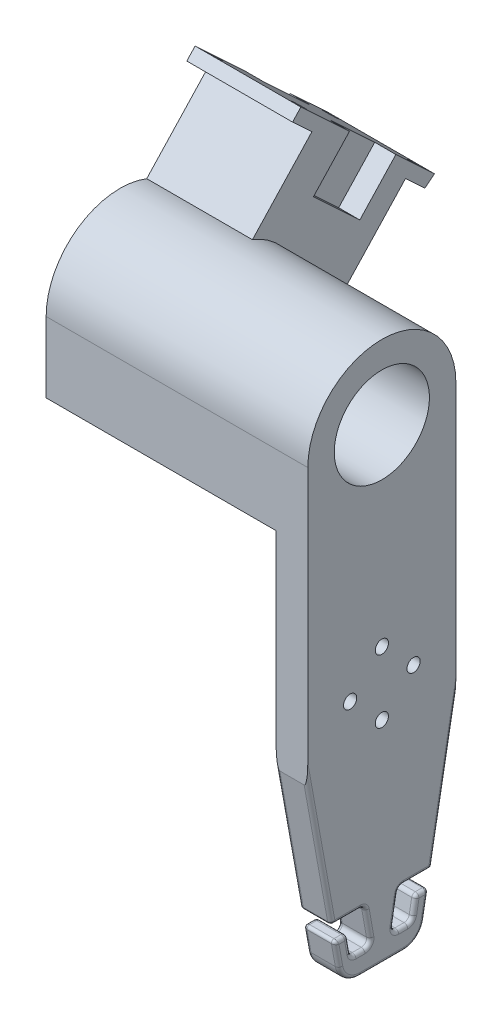
SolidWorks part; units mm, degrees
ref_plane "前视基准面" through (0, 0, 0) normal (0, 0, 1) x (1, 0, 0)
ref_plane "上视基准面" through (0, 0, 0) normal (0, 1, 0) x (1, 0, 0)
ref_plane "右视基准面" through (0, 0, 0) normal (1, 0, 0) x (0, 0, -1)
other "Configuration Table"
sketch "草图1" plane through (0, 0, 0) normal (0, 1, 0) x (1, 0, 0)
  line L1 (-15, 14) -> (15, 14)
  line L2 (-15, 14) -> (-15, -14)
  line L3 (-15, -14) -> (15, -14)
  line L4 (15, 14) -> (15, -14)
  line L5 (-15, 14) -> (15, -14) construction
  line L6 (-15, -14) -> (15, 14) construction
  point P0 (0, 0)
  dimension "D1" = 30
  dimension "D2" = 28
extrude "凸台-拉伸1" add sketch "草图1" along normal blind 67
sketch "草图2" plane through (-15, 0, 0) normal (-1, 0, 0) x (0, 0, 1)
  line L0 (-14, 0) -> (14, 0) construction
  line L1 (-14, 33.5) -> (14, 33.5) construction
  line L2 (-14, 67) -> (-14, 0) construction
  line L3 (14, 67) -> (14, 0) construction
  circle A0 centre (0, 10) radius 8.25
  circle A1 centre (0, 57) radius 8.25
  dimension "D2" = 16.5
  dimension "D1" = 10
extrude "切除-拉伸1" cut sketch "草图2" against normal blind 2.5
sketch "草图3" plane through (-15, 0, 0) normal (-1, 0, 0) x (0, 0, 1)
  point P0 (0, 57)
  point P1 (0, 10)
sketch "草图4" plane through (-12.5, 0, 0) normal (-1, 0, 0) x (0, 0, 1)
  circle A1 centre (0, 57) radius 8.25
  circle A2 centre (0, 57) radius 8.25
  dimension "D1" = 0
extrude "凸台-拉伸2" add sketch "草图4" along normal blind 4
sketch "草图5" plane through (-15, 0, 0) normal (-1, 0, 0) x (0, 0, 1)
  line L0 (14, 67) -> (14, 0) construction
  line L1 (-14, 67) -> (14, 67)
  line L2 (-14, 67) -> (-14, 39)
  line L3 (-14, 39) -> (14, 39)
  line L4 (14, 67) -> (14, 39)
  dimension "D1" = 28
extrude "凸台-拉伸3" add sketch "草图5" along normal blind 33.5
ref_plane "基准面1" through (0, 24.1802, 25.9301) normal (0, 0.682, 0.7314) x (-1, 0, 0)
ref_plane "基准面2" through (0, 42.8198, -39.9301) normal (0, 0.7314, -0.682) x (-1, 0, 0)
ref_plane "基准面3" through (0, 68.0515, -63.459) normal (0, 0.7314, -0.682) x (-1, 0, 0)
sketch "草图6" plane through (0, 68.0515, -63.459) normal (0, 0.7314, -0.682) x (-1, 0, 0)
  line L0 (48.5, 55.9328) -> (-15, 55.9328) construction
  line L10 (34.5, 55.9328) -> (62.5, 55.9328)
  line L11 (34.5, 55.9328) -> (34.5, 16.359)
  line L14 (34.5, 16.359) -> (62.5, 16.359)
  line L15 (62.5, 55.9328) -> (62.5, 16.359)
  line L16 (48.5, 16.359) -> (15, 16.359) construction
  line L17 (62.5, 55.9328) -> (34.5, 16.359) construction
  line L18 (34.5, 55.9328) -> (62.5, 16.359) construction
  line L20 (48.5, 55.9328) -> (48.5, 35.4549) construction
  point P10 (48.5, 36.1459)
  dimension "D1" = 28
extrude "凸台-拉伸4" add sketch "草图6" against normal up to vertex (74.0739 mm away) up to point (-48.5, 39, 14)
sketch "草图10" plane through (-34.5, 0, 0) normal (1, 0, 0) x (0, 0, -1)
  line L3 (14, 39) -> (-14, 39)
  line L4 (-14, 39) -> (0.9766, 25.0341)
  line L5 (0.9766, 25.0341) -> (14, 39)
  line L6 (14, 39) -> (-14, 39)
  line L7 (-14, 39) -> (0.9766, 25.0341)
  line L8 (0.9766, 25.0341) -> (14, 39)
  dimension "D1" = 0
extrude "切除-拉伸4" cut sketch "草图10" against normal through all
sketch "草图11" plane through (-34.5, 0, 0) normal (1, 0, 0) x (0, 0, -1)
  line L3 (-14, 39) -> (-14, 67)
  line L4 (-14, 67) -> (-27.9659, 52.0234)
  line L5 (-27.9659, 52.0234) -> (-14, 39)
  line L6 (-14, 39) -> (-14, 67)
  line L7 (-14, 67) -> (-27.9659, 52.0234)
  line L8 (-27.9659, 52.0234) -> (-14, 39)
  dimension "D1" = 0
extrude "切除-拉伸5" cut sketch "草图11" against normal through all
sketch "草图12" plane through (0, 0, -14) normal (0, 0, -1) x (-1, 0, 0)
  line L0 (15, 39) -> (15, 0) construction
  line L1 (-15, 0) -> (9, 0)
  line L2 (-15, 0) -> (-15, 73.4763)
  line L3 (-15, 73.4763) -> (9, 73.4763)
  line L4 (9, 0) -> (9, 73.4763)
  dimension "D1" = 6
extrude "切除-拉伸6" cut sketch "草图12" against normal through all
sketch "草图13" plane through (-12.5, 0, 0) normal (-1, 0, 0) x (0, 0, 1)
  line L0 (0, 18.25) -> (0, 1.75) construction
  line L1 (-8.25, 10) -> (8.25, 10) construction
  circle A0 centre (0, 10) radius 8.25 construction
  circle A1 centre (0, 10) radius 8.25 construction
  circle A2 centre (0, 16) radius 1.25
  circle A3 centre (6, 10) radius 1.25
  circle A4 centre (-6, 10) radius 1.25
  circle A5 centre (0, 4) radius 1.25
  dimension "D1" = 2.5
  dimension "D2" = 12
  dimension "D3" = 12
extrude "切除-拉伸7" cut sketch "草图13" against normal through all
sketch "草图14" plane through (0, 68.0515, -63.459) normal (0, 0.7314, -0.682) x (1, 0, 0)
  line L4 (-34.5, -55.9328) -> (-34.5, -16.359)
  line L5 (-34.5, -16.359) -> (-62.5, -16.359)
  line L6 (-62.5, -16.359) -> (-62.5, -55.9328)
  line L7 (-62.5, -55.9328) -> (-34.5, -55.9328)
  line L8 (-34.5, -55.9328) -> (-34.5, -16.359)
  line L9 (-34.5, -16.359) -> (-62.5, -16.359)
  line L10 (-62.5, -16.359) -> (-62.5, -55.9328)
  line L11 (-62.5, -55.9328) -> (-34.5, -55.9328)
  dimension "D1" = 0
extrude "切除-拉伸8" cut sketch "草图14" against normal blind 23
sketch "草图15" plane through (-34.5, 0, 0) normal (1, 0, 0) x (0, 0, -1)
  line L0 (-0.3267, 67) -> (14.1799, 82.5565)
  line L1 (14, 67) -> (-14, 67) construction
  line L2 (6.8664, 89.3765) -> (35.8089, 62.3872) construction
  line L3 (14.1799, 82.5565) -> (6.8664, 89.3765)
  line L4 (6.8664, 89.3765) -> (-14, 67)
  line L5 (-14, 67) -> (-0.3267, 67)
  dimension "D1" = 10
extrude "切除-拉伸9" cut sketch "草图15" against normal through all
sketch "草图16" plane through (-34.5, 0, 0) normal (1, 0, 0) x (0, 0, -1)
  line L0 (14, 39) -> (35.8089, 62.3872) construction
  line L1 (14, 39) -> (35.8089, 62.3872)
  line L2 (14, 39) -> (39.4656, 58.9772)
  line L3 (39.4656, 58.9772) -> (35.8089, 62.3872)
  dimension "D1" = 5
extrude "凸台-拉伸5" add sketch "草图16" against normal through all
sketch "草图17" plane through (-62.5, 0, 0) normal (-1, 0, 0) x (0, 0, 1)
  line L0 (0.3267, 67) -> (14, 52.3372)
  line L2 (0.3267, 67) -> (-14.1799, 82.5565) construction
  line L3 (0.3267, 67) -> (14, 67)
  line L4 (14, 67) -> (14, 52.3372)
  line L5 (14, 39) -> (14, 67) construction
extrude "切除-拉伸10" cut sketch "草图17" against normal through all
sketch "草图19" plane through (-34.5, 0, 0) normal (1, 0, 0) x (0, 0, -1)
  line L5 (14.1799, 82.5565) -> (-0.3267, 67)
  line L6 (-0.3267, 67) -> (14, 67)
  line L7 (14, 67) -> (14, 39)
  line L8 (14, 39) -> (39.4656, 58.9772)
  line L9 (39.4656, 58.9772) -> (14.1799, 82.5565)
  line L10 (14.1799, 82.5565) -> (-0.3267, 67)
  line L11 (-0.3267, 67) -> (14, 67)
  line L12 (14, 67) -> (14, 39)
  line L13 (14, 39) -> (39.4656, 58.9772)
  line L14 (39.4656, 58.9772) -> (14.1799, 82.5565)
  dimension "D1" = 0
extrude "切除-拉伸12" cut sketch "草图19" against normal blind 4
sketch "草图20" plane through (-62.5, 0, 0) normal (-1, 0, 0) x (0, 0, 1)
  line L5 (14, 39) -> (14, 52.3372)
  line L6 (14, 52.3372) -> (-14.1799, 82.5565)
  line L7 (-14.1799, 82.5565) -> (-39.4656, 58.9772)
  line L8 (-39.4656, 58.9772) -> (-14, 39)
  line L9 (-14, 39) -> (14, 39)
  line L10 (14, 39) -> (14, 52.3372)
  line L11 (14, 52.3372) -> (-14.1799, 82.5565)
  line L12 (-14.1799, 82.5565) -> (-39.4656, 58.9772)
  line L13 (-39.4656, 58.9772) -> (-14, 39)
  line L14 (-14, 39) -> (14, 39)
  dimension "D1" = 0
extrude "切除-拉伸13" cut sketch "草图20" against normal blind 4
sketch "草图18" plane through (-9, 0, 0) normal (1, 0, 0) x (0, 0, -1)
  line L0 (14, 67) -> (-0.3267, 67) construction
  line L1 (-0.3267, 67) -> (-14, 52.3372) construction
  line L2 (14, 0) -> (14, 67) construction
  line L3 (14, 57.0149) -> (14, 67)
  line L4 (14, 67) -> (4.0149, 67)
  arc A0 (14, 57.0149) -> (4.0149, 67) centre (4.0149, 57.0149) ccw
extrude "切除-拉伸11" cut sketch "草图18" against normal up to surface (29.5 mm away) up to face at (-38.5, 62.9067, -16.2638)
sketch "草图21" plane through (-9, 0, 0) normal (1, 0, 0) x (0, 0, -1)
  line L0 (-14, 0) -> (-14, 52.3372) construction
  line L1 (-0.3267, 67) -> (-14, 52.3372) construction
  line L2 (-0.3267, 67) -> (-14, 52.3372)
  arc A0 (-0.3267, 67) -> (-14, 52.3372) centre (0.6986, 52.3372) ccw
extrude "凸台-拉伸6" add sketch "草图21" against normal through all
sketch "草图22" plane through (-9, 0, 0) normal (1, 0, 0) x (0, 0, -1)
  line L0 (14, 0) -> (14, 57.0149) construction
  line L1 (-14, 0) -> (-14, 52.3372) construction
  line L3 (14, 57.0149) -> (14, 39) construction
  line L4 (-0.3267, 67) -> (4.0149, 67) construction
  line L5 (14, 57.0149) -> (14, 52.3372)
  line L6 (-0.3267, 67) -> (4.0149, 67)
  arc A0 (14, 52.3372) -> (-14, 52.3372) centre (0, 52.3372) ccw
  arc A1 (14, 57.0149) -> (4.0149, 67) centre (4.0149, 57.0149) ccw construction
  arc A2 (-0.3267, 67) -> (-14, 52.3372) centre (0.6986, 52.3372) ccw construction
  arc A3 (14, 57.0149) -> (4.0149, 67) centre (4.0149, 57.0149) ccw
  arc A4 (-0.3267, 67) -> (-14, 52.3372) centre (0.6986, 52.3372) ccw
extrude "切除-拉伸14" cut sketch "草图22" against normal up to surface (29.5 mm away) up to face at (-38.5, 62.2694, -14.567)
sketch "草图23" plane through (-38.5, 0, 0) normal (1, 0, 0) x (0, 0, -1)
  line L0 (12.6113, 80.8744) -> (16.2681, 77.4644)
  line L1 (16.2681, 77.4644) -> (5.0227, 65.4052)
  line L2 (37.634, 57.5403) -> (33.9773, 60.9503)
  line L3 (14, 39) -> (39.4656, 58.9772) construction
  line L4 (14, 52.3372) -> (14, 39)
  line L5 (14, 39) -> (39.4656, 58.9772)
  line L6 (39.4656, 58.9772) -> (14.1799, 82.5565)
  line L7 (14.1799, 82.5565) -> (-0.3267, 67)
  line L11 (12.6113, 80.8744) -> (-0.3267, 67)
  line L13 (39.4656, 58.9772) -> (14.1799, 82.5565) construction
  line L14 (33.9773, 60.9503) -> (14, 39.5273)
  line L16 (14, 0) -> (14, 52.3372) construction
  line L17 (14, 39.5273) -> (14, 39)
  line L18 (14, 52.3372) -> (14, 39) construction
  line L19 (14, 39) -> (37.634, 57.5403)
  arc A0 (14, 52.3372) -> (-14, 52.3372) centre (0, 52.3372) ccw construction
  arc A2 (14, 52.3372) -> (-14, 52.3372) centre (0, 52.3372) ccw
  arc A3 (-0.3267, 67) -> (-14, 52.3372) centre (0.6986, 52.3372) ccw
  arc A4 (5.0227, 65.4052) -> (-14, 52.3372) centre (0, 52.3372) ccw
  arc A5 (-0.3267, 67) -> (-14, 52.3372) centre (0.6986, 52.3372) ccw
  dimension "D2" = 5
  dimension "D3" = 2.3
  dimension "D1" = 0
extrude "切除-拉伸15" cut sketch "草图23" against normal through all
sketch "草图24" plane through (0, 51.2304, -47.7731) normal (0, 0.7314, -0.682) x (1, 0, 0)
  line L0 (-48.5, -45.9328) -> (-48.5, -11.359) construction
  line L1 (-58.5, -45.9328) -> (-38.5, -45.9328) construction
  line L2 (-58.5, -11.359) -> (-38.5, -11.359) construction
  circle A0 centre (-56.5, -43.6328) radius 1.25
  circle A1 centre (-56.5, -13.6328) radius 1.25
  circle A2 centre (-40.5, -13.6328) radius 1.25
  circle A3 centre (-40.5, -43.6328) radius 1.25
  dimension "D1" = 2.5
  dimension "D2" = 2.3
  dimension "D3" = 16
  dimension "D4" = 30
extrude "切除-拉伸16" cut sketch "草图24" against normal blind 10
chamfer "倒角1" [suppressed] distance 2 angle 45
sketch "草图25" plane through (-58.5, 0, 0) normal (-1, 0, 0) x (0, 0, 1)
  circle A0 centre (0, 52.3372) radius 9
  dimension "D1" = 18
extrude "切除-拉伸17" cut sketch "草图25" against normal through all
sketch "草图26" plane through (0, 0, 0) normal (0, 0, 1) x (1, 0, 0)
  line L0 (-58.5, 39) -> (-15, 29)
  line L1 (-15, 39) -> (-15, 0) construction
  line L2 (-15, 29) -> (-15, 39)
  line L3 (-15, 39) -> (-58.5, 39)
  dimension "D1" = 10
extrude "凸台-拉伸7" add sketch "草图26" along normal mid plane 10
sketch "草图27" plane through (0, 0, 14) normal (0, 0, 1) x (1, 0, 0)
  line L0 (-58.5, 45.6686) -> (-40.339, 45.6686) construction
  line L1 (-58.5, 39) -> (-58.5, 52.3372) construction
  circle A0 centre (-46.5, 45.6686) radius 2.1
  dimension "D2" = 4.2
  dimension "D1" = 12
extrude "切除-拉伸18" [suppressed] cut sketch "草图27" against normal blind 10
sketch "草图28" plane through (0, 51.2304, -47.7731) normal (0, 0.7314, -0.682) x (1, 0, 0)
  line L0 (-48.5, -11.359) -> (-48.5, -45.9328) construction
  line L1 (-58.5, -11.359) -> (-38.5, -11.359) construction
  line L2 (-58.5, -45.9328) -> (-38.5, -45.9328) construction
  line L3 (-58.5, -45.9328) -> (-58.5, -11.359) construction
  line L4 (-58.5, -21.359) -> (-54.5, -21.359)
  line L5 (-58.5, -21.359) -> (-58.5, -33.359)
  line L6 (-58.5, -33.359) -> (-54.5, -33.359)
  line L7 (-54.5, -21.359) -> (-54.5, -33.359)
  line L8 (-42.5, -21.359) -> (-42.5, -33.359)
  line L9 (-38.5, -33.359) -> (-42.5, -33.359)
  line L10 (-38.5, -21.359) -> (-38.5, -33.359)
  line L11 (-38.5, -21.359) -> (-42.5, -21.359)
  dimension "D1" = 10
  dimension "D2" = 12
  dimension "D3" = 4
extrude "切除-拉伸19" cut sketch "草图28" against normal blind 10
sketch "草图29" plane through (-9, 0, 0) normal (1, 0, 0) x (0, 0, -1)
  line L2 (-14, 0) -> (14, 0)
  line L3 (0, 0) -> (0, -58.1269) construction
  line L4 (-14, 0) -> (-7.5, -36)
  line L5 (-7.5, -36) -> (7.5, -36)
  line L6 (14, 0) -> (7.5, -36)
  point P11 (0, -36)
  dimension "D1" = 36
  dimension "D2" = 15
extrude "凸台-拉伸8" add sketch "草图29" against normal up to surface (6 mm away) up to face at (-15, 10, 8.25)
sketch "草图30" plane through (-9, 0, 0) normal (1, 0, 0) x (0, 0, -1)
  line L0 (0, 0) -> (0, -47.9288) construction
  line L2 (-14, 0) -> (-7.5, -36) construction
  line L4 (-9.4861, -25) -> (-3.2343, -25)
  line L5 (-3.2343, -25) -> (-2, -32)
  line L6 (-2, -32) -> (-5.7391, -32)
  line L7 (-5.7391, -32) -> (-6.4444, -28)
  line L8 (-6.4444, -28) -> (-8.9444, -28)
  line L9 (-8.9444, -28) -> (-9.4861, -25)
  line L10 (8.9444, -28) -> (9.4861, -25)
  line L11 (6.4444, -28) -> (8.9444, -28)
  line L12 (5.7391, -32) -> (6.4444, -28)
  line L13 (2, -32) -> (5.7391, -32)
  line L14 (3.2343, -25) -> (2, -32)
  line L15 (9.4861, -25) -> (3.2343, -25)
  circle A1 centre (-6, 10) radius 1.25 construction
  dimension "D1" = 10
  dimension "D2" = 42
  dimension "D3" = 3
  dimension "D4" = 2.5
  dimension "D6" = 4
  dimension "D7" = 4
extrude "切除-拉伸20" cut sketch "草图30" against normal through all
fillet "圆角1" radius 0.5 4 edges at (-12, -25, 9.4861) (-12, -25, -9.4861) (-12, -28, -8.9444) (-12, -28, 8.9444)
fillet "圆角2" radius 1 6 edges at (-12, -25, -3.2343) (-12, -32, -5.7391) (-12, -32, -2) (-12, -32, 5.7391) (-12, -32, 2) (-12, -25, 3.2343)
fillet "圆角3" radius 4 2 edges at (-12, -36, -7.5) (-12, -36, 7.5)
fillet "Fillet1" radius 0.7 56 edges at (-9, -28, 7.3953) (-9, -28.1794, 8.7298) (-9, -30.6498, 8.466) (-9, -35.0694, 6.7224) (-9, -36, 0) (-9, -35.0694, -6.7224) (-9, -28, -7.3953) (-9, -28.1794, -8.7298) (-15, -28, -7.3953) (-15, -28.1794, -8.7298) (-15, -28, 7.3953) (-15, -28.1794, 8.7298) (-15, -30.6498, 8.466) (-15, -35.0694, 6.7224) (-15, -36, 0) (-15, -35.0694, -6.7224) (-9, -29.5868, 6.1646) (-9, -31.766, 5.5428) (-9, -32, 4.0459) (-9, -31.6428, 2.4257) (-9, -12.2944, 11.7802) (-9, -24.8837, 9.3889) (-9, -25, 6.5708) (-9, -25.234, 3.4306) (-15, -29.5868, 6.1646) (-15, -31.766, 5.5428) (-15, -32, 4.0459) (-15, -31.6428, 2.4257) (-15, -12.2944, 11.7802) (-15, -24.8837, 9.3889) (-15, -25, 6.5708) (-15, -25.234, 3.4306) (-9, -12.2944, -11.7802) (-9, -24.8837, -9.3889) (-9, -25, -6.5708) (-9, -29.5868, -6.1646) (-9, -31.766, -5.5428) (-9, -32, -4.0459) (-9, -31.6428, -2.4257) (-15, -12.2944, -11.7802) (-15, -24.8837, -9.3889) (-15, -29.5868, -6.1646) (-15, -31.766, -5.5428) (-15, -32, -4.0459) (-15, -31.6428, -2.4257) (-9, -30.6498, -8.466) (-15, -30.6498, -8.466) (-9, -28.3264, 2.6478) (-15, -28.3264, 2.6478) (-15, -25, -6.5708) (-9, -25.234, -3.4306) (-15, -25.234, -3.4306) (-9, -28.3264, -2.6478) (-15, -28.3264, -2.6478) (-12, -28, 6.4444) (-12, -28, -6.4444)
